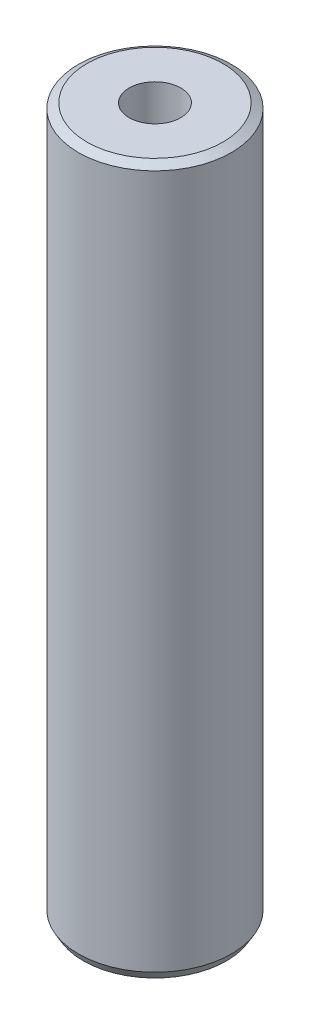
SolidWorks part; units mm, degrees
ref_plane "Front Plane" through (0, 0, 0) normal (0, 0, 1) x (1, 0, 0)
ref_plane "Top Plane" through (0, 0, 0) normal (0, 1, 0) x (1, 0, 0)
ref_plane "Right Plane" through (0, 0, 0) normal (1, 0, 0) x (0, 0, -1)
sketch "Sketch1" plane through (0, 0, 0) normal (0, 1, 0) x (1, 0, 0)
  circle A0 centre (0, 0) radius 30
  dimension "SHAFT_OD" = 60
extrude "Boss-Extrude1" add sketch "Sketch1" along normal blind 277.4016
sketch "Sketch2" plane through (0, 0, 0) normal (0, 1, 0) x (1, 0, 0)
  circle A0 centre (0, 0) radius 10.1236
  dimension "BORE_D" = 20.2473
extrude "Cut-Extrude1" cut sketch "Sketch2" along normal through all
chamfer "Chamfer1" distance 1.9147 angle 60 2 edges at (0, 277.4016, 30) (0, 0, 30) first distance on face at (0, 277.4016, 30) first distance on face at (0, 0, 10.1236)
